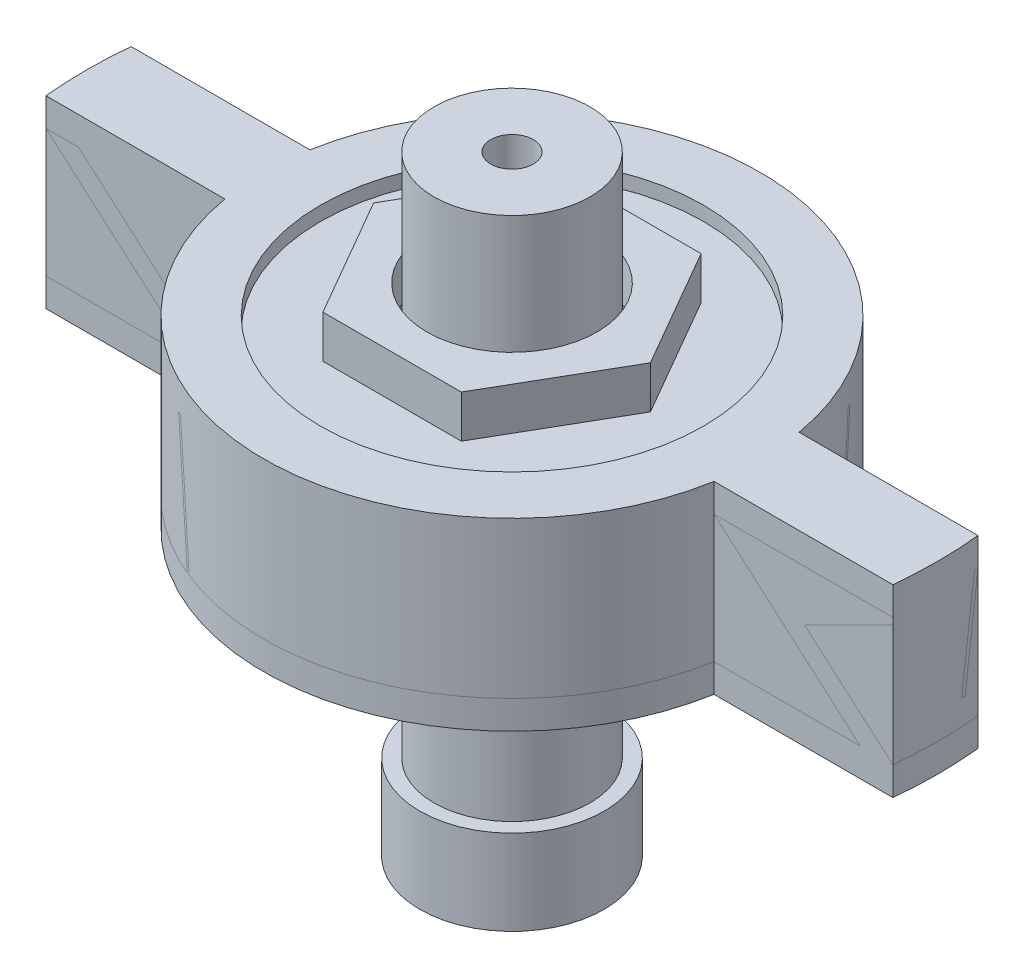
SolidWorks part; units mm, degrees
other "Markup1"
sketch "Sketch15" plane through (-30, 20, -17.5) normal (-0.3209, 0.9299, -0.1799) x (0.8841, 0.3622, 0.2953)
ref_plane "Front Plane" through (0, 0, 0) normal (0, 0, 1) x (1, 0, 0)
ref_plane "Top Plane" through (0, 0, 0) normal (0, 1, 0) x (1, 0, 0)
ref_plane "Right Plane" through (0, 0, 0) normal (1, 0, 0) x (0, 0, -1)
sketch "Sketch2" plane through (0, 0, 0) normal (0, 1, 0) x (1, 0, 0)
  circle A0 centre (0, 0) radius 6.5
  circle A1 centre (0, 0) radius 5.5
  dimension "D1" = 13
  dimension "D2" = 11
extrude "Boss-Extrude1" add sketch "Sketch2" along normal blind 32 contours A1 region at (0, 0, 0)
extrude "Boss-Extrude2" add sketch "Sketch2<3>" against normal blind 6 separate body contours A1 | A0 A1 region at (-6.3162, 0, 0) region at (0, 0, 0)
sketch "Sketch2<3>" plane through (0, 0, 0) normal (0, 1, 0) x (1, 0, 0) same geometry as "Sketch2"
sketch "Sketch5" plane through (0, 32, 0) normal (0, 1, 0) x (1, 0, 0)
  circle A0 centre (0, 0) radius 3.95
  circle M1 centre (0, 0) radius 5.5
  dimension "D1" = 7.9
extrude "Cut-Extrude1" cut sketch "Sketch5" against normal blind 16 contours A0 M1 region at (-5.3444, 32, 0)
sketch "Sketch6" plane through (0, 16, 0) normal (0, 1, 0) x (1, 0, 0)
  circle A0 centre (0, 0) radius 11
  circle A1 centre (0, 0) radius 13.5
  dimension "D1" = 22
  dimension "D2" = 27
extrude "Boss-Extrude4" add sketch "Sketch6" along normal blind 10 separate body
sketch "Sketch7" plane through (0, 26, 0) normal (0, 1, 0) x (1, 0, 0)
  circle A0 centre (0, 0) radius 11.05
  circle A1 centre (0, 0) radius 7.5
  circle A2 centre (0, 0) radius 13.5 construction
  dimension "D1" = 15
  dimension "D2" = 22.1
extrude "Boss-Extrude5" add sketch "Sketch7" against normal blind 3
sketch "Sketch9" plane through (0, 16, 0) normal (0, -1, 0) x (1, 0, 0)
  circle A0 centre (0, 0) radius 17.5
  circle A1 centre (0, 0) radius 13.5
  dimension "D1" = 35
  dimension "D2" = 27
extrude "Boss-Extrude6" add sketch "Sketch9" against normal blind 11
sketch "Sketch10" plane through (0, 26, 0) normal (0, 1, 0) x (1, 0, 0)
  line L1 (9.7572, 0) -> (4.8786, 8.45)
  line L2 (4.8786, 8.45) -> (-4.8786, 8.45)
  line L3 (-4.8786, 8.45) -> (-9.7572, 0)
  line L4 (-9.7572, 0) -> (-4.8786, -8.45)
  line L5 (-4.8786, -8.45) -> (4.8786, -8.45)
  line L6 (4.8786, -8.45) -> (9.7572, 0)
  circle A0 centre (0, 0) radius 8.45 construction
  circle A1 centre (0, 0) radius 6
  dimension "D2" = 12
  dimension "D1" = 16.9
extrude "Boss-Extrude7" add sketch "Sketch10" along normal blind 3
chamfer "Chamfer2" distance 2 angle 60 1 edges at (0, 23, 7.5) first distance on face at (0, 23, 7.5)
sketch "Sketch11" plane through (0, 16, 0) normal (0, -1, 0) x (1, 0, 0)
  line L0 (-30, 0) -> (30, 0)
  line L1 (-30, -3) -> (30, -3)
  line L2 (-30, 3) -> (30, 3)
  circle A0 centre (0, 0) radius 30
  circle A1 centre (0, 0) radius 17.5
  circle M2 centre (0, 0) radius 17.5
  dimension "D1" = 60
  dimension "D4" = 35
  dimension "D2" = 3
  dimension "D3" = 3
extrude "Boss-Extrude8" add sketch "Sketch11" against normal blind 11 contours L0 A0 L2 M2 | L1 A0 L0 M2 | L2 A0 L0 M2 | L0 A0 L1 M2 region at (23.6818, 16, 1.5022) region at (23.6818, 16, -1.5022) region at (-23.6818, 16, -1.5022) region at (-23.6818, 16, 1.5022)
sketch "Sketch12" plane through (0, 32, 0) normal (0, 1, 0) x (1, 0, 0)
  circle A0 centre (0, 0) radius 5.5
  circle A1 centre (0, 0) radius 5.5
  circle A2 centre (0, 0) radius 4
  dimension "D1" = 11
  dimension "D2" = 8
extrude "Boss-Extrude9" add sketch "Sketch12" against normal offset from surface 6.8 and the other way blind 5 separate body contours A0 A2 region at (-5.3444, 32, 0) up to face at (0, 16, 3.95)
combine bodies "Combine1" operation type add bodies to combine 103 102
ref_plane "Plane1" through (0, 20.5, 0) normal (0, 1, 0) x (1, 0, 0)
mirror "Mirror1" about plane through (0, 20.5, 0) normal (0, 1, 0) of bodies 109
sketch "Sketch16" plane through (0, 37, 0) normal (0, 1, 0) x (1, 0, 0)
  circle A0 centre (0, 0) radius 4
  dimension "D1" = 8
extrude "Boss-Extrude10" add sketch "Sketch16" against normal blind 2.9
sketch "Sketch17" plane through (0, 37, 0) normal (0, 1, 0) x (1, 0, 0)
  circle A0 centre (0, 0) radius 1.5
  dimension "D1" = 3
extrude "Cut-Extrude2" cut sketch "Sketch17" against normal blind 10
